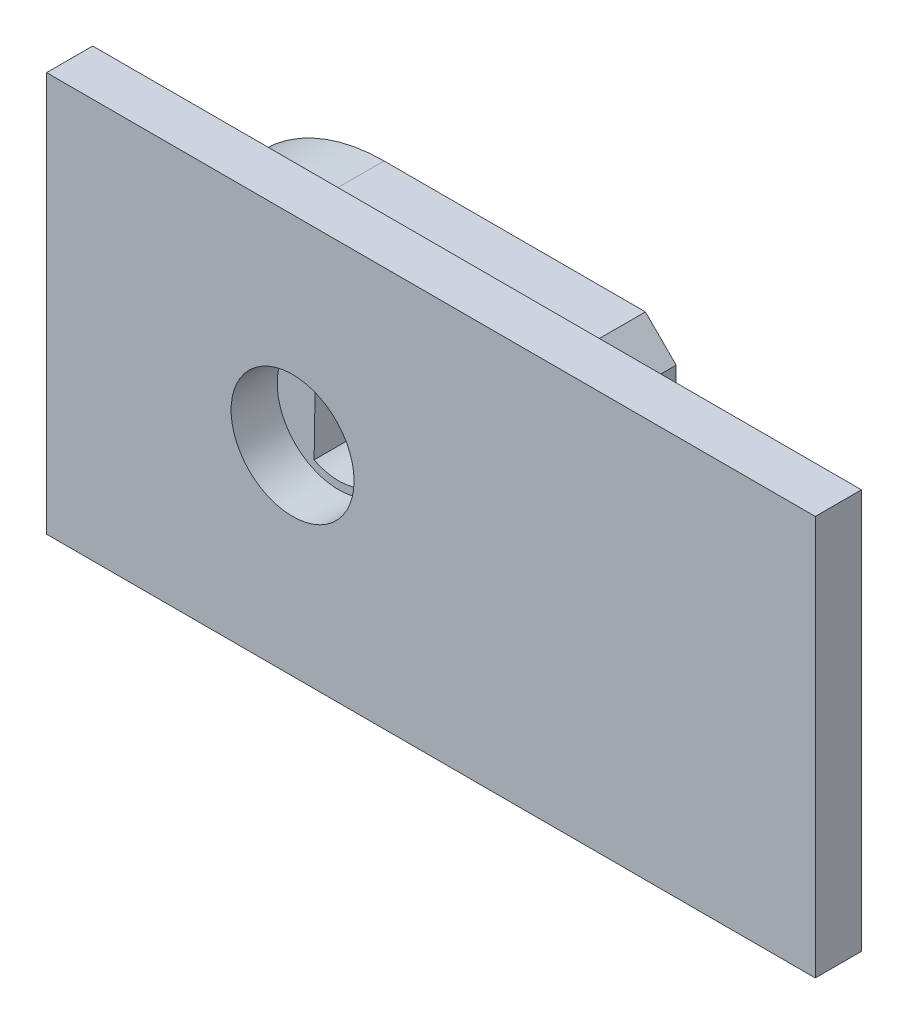
SolidWorks part; units mm, degrees
ref_plane "前视基准面" through (0, 0, 0) normal (0, 0, 1) x (1, 0, 0)
ref_plane "上视基准面" through (0, 0, 0) normal (0, 1, 0) x (1, 0, 0)
ref_plane "右视基准面" through (0, 0, 0) normal (1, 0, 0) x (0, 0, -1)
sketch "草图1" plane through (0, 0, 0) normal (0, 0, 1) x (1, 0, 0)
  line L0 (0, 0) -> (25, 0)
  line L1 (25, 0) -> (25, 13)
  line L2 (25, 13) -> (0, 13)
  line L3 (0, 13) -> (0, 0)
extrude "凸台-拉伸1" add sketch "草图1" along normal blind 1.5
sketch "草图2" plane through (0, 0, 1.5) normal (0, 0, 1) x (1, 0, 0)
  line L0 (0, 13) -> (0, 0) construction
  line L2 (0, 6.5) -> (27.1052, 6.5) construction
  circle A0 centre (8, 6.5) radius 2
  dimension "D1" = 8
extrude "切除-拉伸1" cut sketch "草图2" against normal blind 2.8 contours A0 | A0 region at (8, 6.5, 1.5)
sketch "草图3" plane through (0, 0, 0) normal (0, 0, -1) x (-1, 0, 0)
  line L0 (0, 6.5) -> (-27.3666, 6.5) construction
  line L1 (0, 13) -> (0, 0) construction
  line L2 (-8, 6.5) -> (-7.25, 6.5) construction
  line L3 (-1.4762, 1) -> (-16.4762, 1)
  line L4 (-1.4762, 1) -> (-1.4762, 12)
  line L5 (-1.4762, 12) -> (-16.4762, 12)
  line L6 (-16.4762, 1) -> (-16.4762, 12)
  line L7 (-1.4762, 1) -> (-16.4762, 12) construction
  line L8 (-1.4762, 12) -> (-16.4762, 1) construction
  line L9 (-7.25, 8.0811) -> (-7.2006, 4.9432)
  arc A0 (-7.25, 8.0811) -> (-7.2006, 4.9432) centre (-8, 6.5) ccw
  point P5 (-8.9762, 6.5)
extrude "凸台-拉伸2" add sketch "草图3" along normal blind 2.5
fillet "圆角1" radius 5.5 2 edges at (1.4762, 1, -1.25) (1.4762, 12, -1.25)
chamfer "倒角1" distance 1 angle 45 2 edges at (16.4762, 1, -1.25) (16.4762, 12, -1.25)
